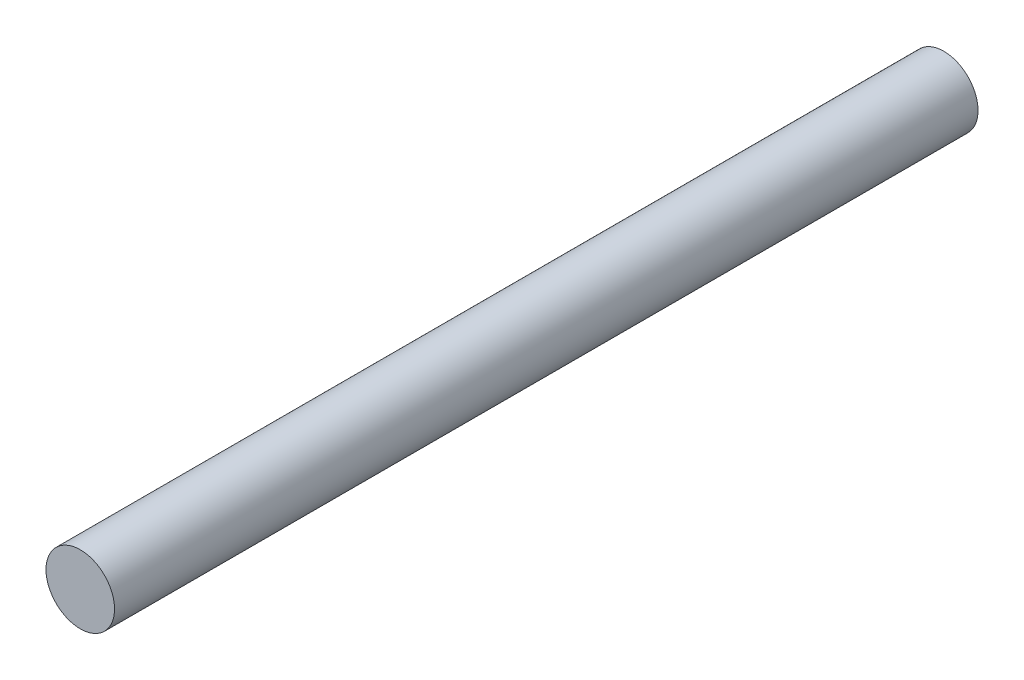
SolidWorks part; units mm, degrees
material "AISI 4130 Steel, annealed at 865C"
ref_plane "X-Y Datum" through (0, 0, 0) normal (0, 0, 1) x (1, 0, 0)
ref_plane "X-Z Datum" through (0, 0, 0) normal (0, 1, 0) x (1, 0, 0)
ref_plane "Y-Z Datum" through (0, 0, 0) normal (1, 0, 0) x (0, 0, -1)
sketch "Sketch9" plane through (0, 0, 0) normal (0, 1, 0) x (1, 0, 0)
  line L0 (16.002, 0) -> (0, 0)
  line L1 (0, 0) -> (0, -389.0916)
  line L2 (0, -389.0916) -> (-72.2493, -524.9728)
  dimension "D1" = 153.895
  dimension "D2" = 28
  dimension "D3" = 389.0916
  dimension "D5" = 16.002
sketch "Sketch5" plane through (0, 0, 0) normal (0, 1, 0) x (1, 0, 0)
  line L0 (7.9375, -262.0916) -> (7.9375, -22.1615)
  line L1 (7.9375, -22.1615) -> (9.525, -22.1615)
  line L2 (9.525, -22.1615) -> (9.525, -262.0916)
  line L3 (9.525, -262.0916) -> (7.9375, -262.0916)
  line L5 (16.002, 0) -> (0, 0) construction
  line L6 (0, 0) -> (0, -389.0916) construction
  line L7 (0, -389.0916) -> (9.525, -389.0916) construction
  line L8 (12.5602, -369.8416) -> (0, -369.8416) construction
  dimension "D1" = 1.5875
  dimension "D2" = 22.1615
  dimension "D3" = 7.9375
  dimension "D4" = 19.25
  dimension "D5" = 127
revolve "Revolve2" add sketch "Sketch5" angle 360 about L1
sketch "Sketch6" plane through (0, 0, 0) normal (0, 1, 0) x (1, 0, 0)
  circle A0 centre (0, -33.1635) radius 1.5875 construction
  circle A1 centre (0, -33.1635) radius 1.5875
sketch "Sketch7" plane through (0, 0, 0) normal (1, 0, 0) x (0, 0, -1)
  circle A2 centre (-39.196, 0) radius 1.5875
  circle A4 centre (-39.196, 0) radius 1.5875 construction
extrude "Cut-Extrude5" [suppressed] cut sketch "Sketch7" against normal through all both and the other way through all
extrude "Cut-Extrude6" [suppressed] cut sketch "Sketch6" against normal through all both and the other way through all
sketch "Sketch8" plane through (0, 0, 0) normal (0, 0, 1) x (1, 0, 0)
  line L0 (9.2357, -0.808) -> (8.6817, -0.254)
  line L1 (8.6817, -0.254) -> (8.6817, 0.254)
  line L2 (8.6817, 0.254) -> (9.2357, 0.808)
  line L3 (8.6817, 0) -> (0, 0) construction
  line L4 (8.9551, -2.3995) -> (8.5057, -1.7577)
  line L5 (8.5057, -1.7577) -> (8.5939, -1.2574)
  line L6 (8.5939, -1.2574) -> (9.2357, -0.808)
  line L7 (8.4024, -3.9181) -> (8.0713, -3.208)
  line L8 (8.0713, -3.208) -> (8.245, -2.7306)
  line L9 (8.245, -2.7306) -> (8.9551, -2.3995)
  line L10 (7.5944, -5.3176) -> (7.3916, -4.5608)
  line L11 (7.3916, -4.5608) -> (7.6456, -4.1209)
  line L12 (7.6456, -4.1209) -> (8.4024, -3.9181)
  line L13 (6.5556, -6.5556) -> (6.4873, -5.7751)
  line L14 (6.4873, -5.7751) -> (6.8138, -5.3859)
  line L15 (6.8138, -5.3859) -> (7.5944, -5.3176)
  line L16 (5.3176, -7.5944) -> (5.3859, -6.8138)
  line L17 (5.3859, -6.8138) -> (5.7751, -6.4873)
  line L18 (5.7751, -6.4873) -> (6.5556, -6.5556)
  line L19 (3.9181, -8.4024) -> (4.1209, -7.6456)
  line L20 (4.1209, -7.6456) -> (4.5608, -7.3916)
  line L21 (4.5608, -7.3916) -> (5.3176, -7.5944)
  line L22 (2.3995, -8.9551) -> (2.7306, -8.245)
  line L23 (2.7306, -8.245) -> (3.208, -8.0713)
  line L24 (3.208, -8.0713) -> (3.9181, -8.4024)
  line L25 (0.808, -9.2357) -> (1.2574, -8.5939)
  line L26 (1.2574, -8.5939) -> (1.7577, -8.5057)
  line L27 (1.7577, -8.5057) -> (2.3995, -8.9551)
  line L28 (-0.808, -9.2357) -> (-0.254, -8.6817)
  line L29 (-0.254, -8.6817) -> (0.254, -8.6817)
  line L30 (0.254, -8.6817) -> (0.808, -9.2357)
  line L31 (-2.3995, -8.9551) -> (-1.7577, -8.5057)
  line L32 (-1.7577, -8.5057) -> (-1.2574, -8.5939)
  line L33 (-1.2574, -8.5939) -> (-0.808, -9.2357)
  line L34 (-3.9181, -8.4024) -> (-3.208, -8.0713)
  line L35 (-3.208, -8.0713) -> (-2.7306, -8.245)
  line L36 (-2.7306, -8.245) -> (-2.3995, -8.9551)
  line L37 (-5.3176, -7.5944) -> (-4.5608, -7.3916)
  line L38 (-4.5608, -7.3916) -> (-4.1209, -7.6456)
  line L39 (-4.1209, -7.6456) -> (-3.9181, -8.4024)
  line L40 (-6.5556, -6.5556) -> (-5.7751, -6.4873)
  line L41 (-5.7751, -6.4873) -> (-5.3859, -6.8138)
  line L42 (-5.3859, -6.8138) -> (-5.3176, -7.5944)
  line L43 (-7.5944, -5.3176) -> (-6.8138, -5.3859)
  line L44 (-6.8138, -5.3859) -> (-6.4873, -5.7751)
  line L45 (-6.4873, -5.7751) -> (-6.5556, -6.5556)
  line L46 (-8.4024, -3.9181) -> (-7.6456, -4.1209)
  line L47 (-7.6456, -4.1209) -> (-7.3916, -4.5608)
  line L48 (-7.3916, -4.5608) -> (-7.5944, -5.3176)
  line L49 (-8.9551, -2.3995) -> (-8.245, -2.7306)
  line L50 (-8.245, -2.7306) -> (-8.0713, -3.208)
  line L51 (-8.0713, -3.208) -> (-8.4024, -3.9181)
  line L52 (-9.2357, -0.808) -> (-8.5939, -1.2574)
  line L53 (-8.5939, -1.2574) -> (-8.5057, -1.7577)
  line L54 (-8.5057, -1.7577) -> (-8.9551, -2.3995)
  line L55 (-9.2357, 0.808) -> (-8.6817, 0.254)
  line L56 (-8.6817, 0.254) -> (-8.6817, -0.254)
  line L57 (-8.6817, -0.254) -> (-9.2357, -0.808)
  line L58 (-8.9551, 2.3995) -> (-8.5057, 1.7577)
  line L59 (-8.5057, 1.7577) -> (-8.5939, 1.2574)
  line L60 (-8.5939, 1.2574) -> (-9.2357, 0.808)
  line L61 (-8.4024, 3.9181) -> (-8.0713, 3.208)
  line L62 (-8.0713, 3.208) -> (-8.245, 2.7306)
  line L63 (-8.245, 2.7306) -> (-8.9551, 2.3995)
  line L64 (-7.5944, 5.3176) -> (-7.3916, 4.5608)
  line L65 (-7.3916, 4.5608) -> (-7.6456, 4.1209)
  line L66 (-7.6456, 4.1209) -> (-8.4024, 3.9181)
  line L67 (-6.5556, 6.5556) -> (-6.4873, 5.7751)
  line L68 (-6.4873, 5.7751) -> (-6.8138, 5.3859)
  line L69 (-6.8138, 5.3859) -> (-7.5944, 5.3176)
  line L70 (-5.3176, 7.5944) -> (-5.3859, 6.8138)
  line L71 (-5.3859, 6.8138) -> (-5.7751, 6.4873)
  line L72 (-5.7751, 6.4873) -> (-6.5556, 6.5556)
  line L73 (-3.9181, 8.4024) -> (-4.1209, 7.6456)
  line L74 (-4.1209, 7.6456) -> (-4.5608, 7.3916)
  line L75 (-4.5608, 7.3916) -> (-5.3176, 7.5944)
  line L76 (-2.3995, 8.9551) -> (-2.7306, 8.245)
  line L77 (-2.7306, 8.245) -> (-3.208, 8.0713)
  line L78 (-3.208, 8.0713) -> (-3.9181, 8.4024)
  line L79 (-0.808, 9.2357) -> (-1.2574, 8.5939)
  line L80 (-1.2574, 8.5939) -> (-1.7577, 8.5057)
  line L81 (-1.7577, 8.5057) -> (-2.3995, 8.9551)
  line L82 (0.808, 9.2357) -> (0.254, 8.6817)
  line L83 (0.254, 8.6817) -> (-0.254, 8.6817)
  line L84 (-0.254, 8.6817) -> (-0.808, 9.2357)
  line L85 (2.3995, 8.9551) -> (1.7577, 8.5057)
  line L86 (1.7577, 8.5057) -> (1.2574, 8.5939)
  line L87 (1.2574, 8.5939) -> (0.808, 9.2357)
  line L88 (3.9181, 8.4024) -> (3.208, 8.0713)
  line L89 (3.208, 8.0713) -> (2.7306, 8.245)
  line L90 (2.7306, 8.245) -> (2.3995, 8.9551)
  line L91 (5.3176, 7.5944) -> (4.5608, 7.3916)
  line L92 (4.5608, 7.3916) -> (4.1209, 7.6456)
  line L93 (4.1209, 7.6456) -> (3.9181, 8.4024)
  line L94 (6.5556, 6.5556) -> (5.7751, 6.4873)
  line L95 (5.7751, 6.4873) -> (5.3859, 6.8138)
  line L96 (5.3859, 6.8138) -> (5.3176, 7.5944)
  line L97 (7.5944, 5.3176) -> (6.8138, 5.3859)
  line L98 (6.8138, 5.3859) -> (6.4873, 5.7751)
  line L99 (6.4873, 5.7751) -> (6.5556, 6.5556)
  line L100 (8.4024, 3.9181) -> (7.6456, 4.1209)
  line L101 (7.6456, 4.1209) -> (7.3916, 4.5608)
  line L102 (7.3916, 4.5608) -> (7.5944, 5.3176)
  line L103 (8.9551, 2.3995) -> (8.245, 2.7306)
  line L104 (8.245, 2.7306) -> (8.0713, 3.208)
  line L105 (8.0713, 3.208) -> (8.4024, 3.9181)
  line L106 (9.2357, 0.808) -> (8.5939, 1.2574)
  line L107 (8.5939, 1.2574) -> (8.5057, 1.7577)
  line L108 (8.5057, 1.7577) -> (8.9551, 2.3995)
  circle A0 centre (0, 0) radius 12.7
  circle A1 centre (0, 0) radius 9.271 construction
  circle A2 centre (0, 0) radius 8.6854 construction
  point P153 (0, 0)
  dimension "D1" = 25.4
  dimension "D4" = 18.542
  dimension "D6" = 17.3708
  dimension "D2" = 0.508
  dimension "D3" = 135
  dimension "D5" = 36
ref_plane "Plane1" through (0, 0, 47.5615) normal (0, 0, -1) x (-1, 0, 0)
sketch "Sketch10" plane through (0, 0, 47.5615) normal (0, 0, -1) x (-1, 0, 0)
  circle A0 centre (0, 0) radius 7.9375
  dimension "D1" = 15.875
extrude "Boss-Extrude1" add sketch "Sketch10" against normal up to surface (214.5301 mm away) up to face at (-9.525, 0, 262.0916)
sketch "Sketch11" plane through (0, 0, 22.1615) normal (0, 0, -1) x (-1, 0, 0)
  line L0 (0, 9.525) -> (13.3548, 9.525) construction
  line L1 (0, 9.525) -> (0, 15.4312) construction
  line L2 (-9.525, 0) -> (-9.525, 9.1744) construction
  line L3 (-9.525, 0) -> (-16.674, 0) construction
  circle A0 centre (0, 0) radius 9.525 construction
  point P0 (0, 9.525)
  point P1 (-9.525, 0)
sketch "Sketch12" plane through (0, 0, 0) normal (0, 0, 1) x (1, 0, 0)
  line L0 (9.2357, -0.808) -> (8.6817, -0.254)
  line L1 (8.6817, -0.254) -> (8.6817, 0.254)
  line L2 (8.6817, 0.254) -> (9.2357, 0.808)
  line L3 (8.6817, 0) -> (0, 0) construction
  line L4 (8.9551, -2.3995) -> (8.5057, -1.7577)
  line L5 (8.5057, -1.7577) -> (8.5939, -1.2574)
  line L6 (8.5939, -1.2574) -> (9.2357, -0.808)
  line L7 (8.4024, -3.9181) -> (8.0713, -3.208)
  line L8 (8.0713, -3.208) -> (8.245, -2.7306)
  line L9 (8.245, -2.7306) -> (8.9551, -2.3995)
  line L10 (7.5944, -5.3176) -> (7.3916, -4.5608)
  line L11 (7.3916, -4.5608) -> (7.6456, -4.1209)
  line L12 (7.6456, -4.1209) -> (8.4024, -3.9181)
  line L13 (6.5556, -6.5556) -> (6.4873, -5.7751)
  line L14 (6.4873, -5.7751) -> (6.8138, -5.3859)
  line L15 (6.8138, -5.3859) -> (7.5944, -5.3176)
  line L16 (5.3176, -7.5944) -> (5.3859, -6.8138)
  line L17 (5.3859, -6.8138) -> (5.7751, -6.4873)
  line L18 (5.7751, -6.4873) -> (6.5556, -6.5556)
  line L19 (3.9181, -8.4024) -> (4.1209, -7.6456)
  line L20 (4.1209, -7.6456) -> (4.5608, -7.3916)
  line L21 (4.5608, -7.3916) -> (5.3176, -7.5944)
  line L22 (2.3995, -8.9551) -> (2.7306, -8.245)
  line L23 (2.7306, -8.245) -> (3.208, -8.0713)
  line L24 (3.208, -8.0713) -> (3.9181, -8.4024)
  line L25 (0.808, -9.2357) -> (1.2574, -8.5939)
  line L26 (1.2574, -8.5939) -> (1.7577, -8.5057)
  line L27 (1.7577, -8.5057) -> (2.3995, -8.9551)
  line L28 (-0.808, -9.2357) -> (-0.254, -8.6817)
  line L29 (-0.254, -8.6817) -> (0.254, -8.6817)
  line L30 (0.254, -8.6817) -> (0.808, -9.2357)
  line L31 (-2.3995, -8.9551) -> (-1.7577, -8.5057)
  line L32 (-1.7577, -8.5057) -> (-1.2574, -8.5939)
  line L33 (-1.2574, -8.5939) -> (-0.808, -9.2357)
  line L34 (-3.9181, -8.4024) -> (-3.208, -8.0713)
  line L35 (-3.208, -8.0713) -> (-2.7306, -8.245)
  line L36 (-2.7306, -8.245) -> (-2.3995, -8.9551)
  line L37 (-5.3176, -7.5944) -> (-4.5608, -7.3916)
  line L38 (-4.5608, -7.3916) -> (-4.1209, -7.6456)
  line L39 (-4.1209, -7.6456) -> (-3.9181, -8.4024)
  line L40 (-6.5556, -6.5556) -> (-5.7751, -6.4873)
  line L41 (-5.7751, -6.4873) -> (-5.3859, -6.8138)
  line L42 (-5.3859, -6.8138) -> (-5.3176, -7.5944)
  line L43 (-7.5944, -5.3176) -> (-6.8138, -5.3859)
  line L44 (-6.8138, -5.3859) -> (-6.4873, -5.7751)
  line L45 (-6.4873, -5.7751) -> (-6.5556, -6.5556)
  line L46 (-8.4024, -3.9181) -> (-7.6456, -4.1209)
  line L47 (-7.6456, -4.1209) -> (-7.3916, -4.5608)
  line L48 (-7.3916, -4.5608) -> (-7.5944, -5.3176)
  line L49 (-8.9551, -2.3995) -> (-8.245, -2.7306)
  line L50 (-8.245, -2.7306) -> (-8.0713, -3.208)
  line L51 (-8.0713, -3.208) -> (-8.4024, -3.9181)
  line L52 (-9.2357, -0.808) -> (-8.5939, -1.2574)
  line L53 (-8.5939, -1.2574) -> (-8.5057, -1.7577)
  line L54 (-8.5057, -1.7577) -> (-8.9551, -2.3995)
  line L55 (-9.2357, 0.808) -> (-8.6817, 0.254)
  line L56 (-8.6817, 0.254) -> (-8.6817, -0.254)
  line L57 (-8.6817, -0.254) -> (-9.2357, -0.808)
  line L58 (-8.9551, 2.3995) -> (-8.5057, 1.7577)
  line L59 (-8.5057, 1.7577) -> (-8.5939, 1.2574)
  line L60 (-8.5939, 1.2574) -> (-9.2357, 0.808)
  line L61 (-8.4024, 3.9181) -> (-8.0713, 3.208)
  line L62 (-8.0713, 3.208) -> (-8.245, 2.7306)
  line L63 (-8.245, 2.7306) -> (-8.9551, 2.3995)
  line L64 (-7.5944, 5.3176) -> (-7.3916, 4.5608)
  line L65 (-7.3916, 4.5608) -> (-7.6456, 4.1209)
  line L66 (-7.6456, 4.1209) -> (-8.4024, 3.9181)
  line L67 (-6.5556, 6.5556) -> (-6.4873, 5.7751)
  line L68 (-6.4873, 5.7751) -> (-6.8138, 5.3859)
  line L69 (-6.8138, 5.3859) -> (-7.5944, 5.3176)
  line L70 (-5.3176, 7.5944) -> (-5.3859, 6.8138)
  line L71 (-5.3859, 6.8138) -> (-5.7751, 6.4873)
  line L72 (-5.7751, 6.4873) -> (-6.5556, 6.5556)
  line L73 (-3.9181, 8.4024) -> (-4.1209, 7.6456)
  line L74 (-4.1209, 7.6456) -> (-4.5608, 7.3916)
  line L75 (-4.5608, 7.3916) -> (-5.3176, 7.5944)
  line L76 (-2.3995, 8.9551) -> (-2.7306, 8.245)
  line L77 (-2.7306, 8.245) -> (-3.208, 8.0713)
  line L78 (-3.208, 8.0713) -> (-3.9181, 8.4024)
  line L79 (-0.808, 9.2357) -> (-1.2574, 8.5939)
  line L80 (-1.2574, 8.5939) -> (-1.7577, 8.5057)
  line L81 (-1.7577, 8.5057) -> (-2.3995, 8.9551)
  line L82 (0.808, 9.2357) -> (0.254, 8.6817)
  line L83 (0.254, 8.6817) -> (-0.254, 8.6817)
  line L84 (-0.254, 8.6817) -> (-0.808, 9.2357)
  line L85 (2.3995, 8.9551) -> (1.7577, 8.5057)
  line L86 (1.7577, 8.5057) -> (1.2574, 8.5939)
  line L87 (1.2574, 8.5939) -> (0.808, 9.2357)
  line L88 (3.9181, 8.4024) -> (3.208, 8.0713)
  line L89 (3.208, 8.0713) -> (2.7306, 8.245)
  line L90 (2.7306, 8.245) -> (2.3995, 8.9551)
  line L91 (5.3176, 7.5944) -> (4.5608, 7.3916)
  line L92 (4.5608, 7.3916) -> (4.1209, 7.6456)
  line L93 (4.1209, 7.6456) -> (3.9181, 8.4024)
  line L94 (6.5556, 6.5556) -> (5.7751, 6.4873)
  line L95 (5.7751, 6.4873) -> (5.3859, 6.8138)
  line L96 (5.3859, 6.8138) -> (5.3176, 7.5944)
  line L97 (7.5944, 5.3176) -> (6.8138, 5.3859)
  line L98 (6.8138, 5.3859) -> (6.4873, 5.7751)
  line L99 (6.4873, 5.7751) -> (6.5556, 6.5556)
  line L100 (8.4024, 3.9181) -> (7.6456, 4.1209)
  line L101 (7.6456, 4.1209) -> (7.3916, 4.5608)
  line L102 (7.3916, 4.5608) -> (7.5944, 5.3176)
  line L103 (8.9551, 2.3995) -> (8.245, 2.7306)
  line L104 (8.245, 2.7306) -> (8.0713, 3.208)
  line L105 (8.0713, 3.208) -> (8.4024, 3.9181)
  line L106 (9.2357, 0.808) -> (8.5939, 1.2574)
  line L107 (8.5939, 1.2574) -> (8.5057, 1.7577)
  line L108 (8.5057, 1.7577) -> (8.9551, 2.3995)
  circle A0 centre (0, 0) radius 12.7
  circle A1 centre (0, 0) radius 9.271 construction
  circle A2 centre (0, 0) radius 8.6854 construction
  point P153 (0, 0)
  dimension "D1" = 25.4
  dimension "D4" = 18.542
  dimension "D6" = 17.3708
  dimension "D2" = 0.508
  dimension "D3" = 135
  dimension "D5" = 36
